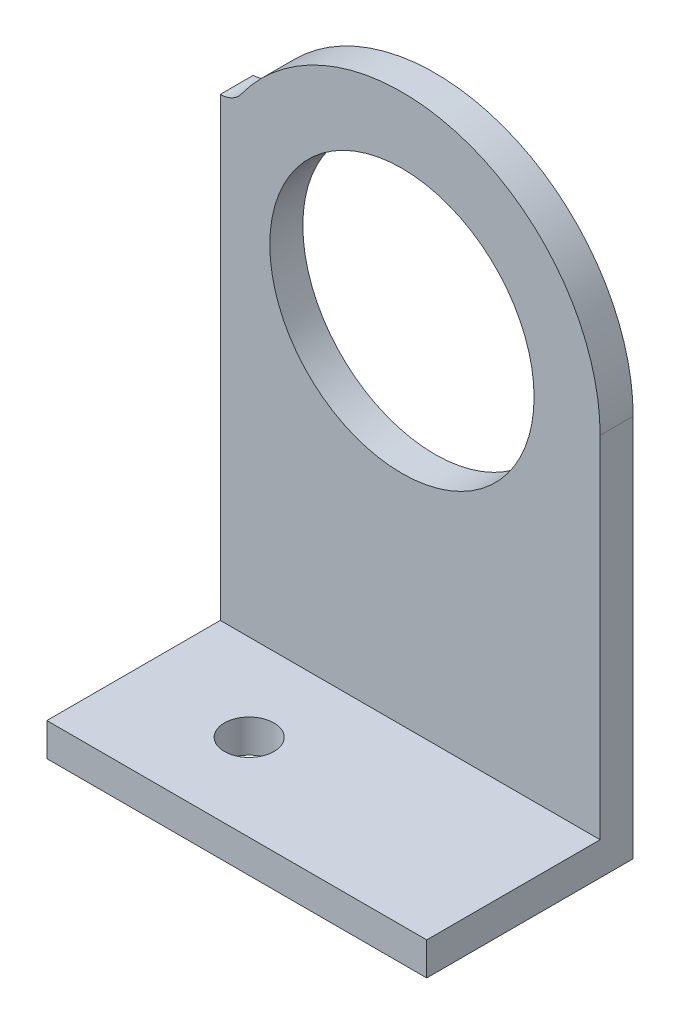
SolidWorks part; units mm, degrees
ref_plane "Front Plane" through (0, 0, 0) normal (0, 0, 1) x (1, 0, 0)
ref_plane "Top Plane" through (0, 0, 0) normal (0, 1, 0) x (1, 0, 0)
ref_plane "Right Plane" through (0, 0, 0) normal (1, 0, 0) x (0, 0, -1)
sketch "Sketch1" plane through (0, 0, 0) normal (0, 1, 0) x (1, 0, 0)
  line L1 (0, 0) -> (23, 0)
  line L2 (0, 0) -> (0, 12.5)
  line L3 (0, 12.5) -> (23, 12.5)
  line L4 (23, 0) -> (23, 12.5)
  dimension "D1" = 12.5
  dimension "D2" = 23
extrude "Boss-Extrude1" add sketch "Sketch1" along normal blind 2
sketch "Sketch2" plane through (0, 0, -12.5) normal (0, 0, -1) x (-1, 0, 0)
  line L1 (-23, 2) -> (0, 2)
  line L2 (-23, 2) -> (-23, 35.2062)
  line L3 (-23, 35.2062) -> (0, 35.2062)
  line L4 (0, 2) -> (0, 35.2062)
extrude "Boss-Extrude2" add sketch "Sketch2" against normal blind 2
sketch "Sketch3" plane through (0, 2, 0) normal (0, 1, 0) x (1, 0, 0)
  line L0 (0, 5.25) -> (23, 5.25) construction
  line L1 (0, 10.5) -> (0, 0) construction
  line L2 (23, 0) -> (23, 10.5) construction
  circle A0 centre (7, 5.25) radius 1.5
  dimension "D1" = 3
  dimension "D2" = 5.5
extrude "Cut-Extrude1" cut sketch "Sketch3" against normal blind 2 contours A0
sketch "Sketch4" plane through (0, 0, -12.5) normal (0, 0, -1) x (-1, 0, 0)
  line L1 (0, 35.2062) -> (0, 0) construction
  line L2 (0, 35.2062) -> (-23, 35.2062) construction
  circle A0 centre (-11, 23.2062) radius 8
  point P2 (-9.8668, 15.3728)
  point P3 (0, 0)
  point P4 (-10.1809, 18.5943)
  point P7 (-11, 20.2323)
  point P8 (0, 0)
  point P9 (-11, 19.1051)
  point P10 (-11, 20.214)
  dimension "D1" = 16
  dimension "D2" = 3
  dimension "D3" = 4
sketch "Sketch5" plane through (0, 0, -12.5) normal (0, 0, -1) x (-1, 0, 0)
sketch "Sketch6" plane through (0, 0, -12.5) normal (0, 0, -1) x (-1, 0, 0)
  line L0 (-23, 35.2062) -> (-23, 0) construction
  line L1 (0, 35.2062) -> (0, 0) construction
  arc A0 (-23, 23.2062) -> (-1.2728, 30.2334) centre (-11, 23.2062) cw
  arc A1 (-1.2728, 30.2334) -> (0, 29.5827) centre (0, 31.1529) ccw
extrude "Cut-Extrude2" cut sketch "Sketch4" against normal blind 2 contours A0
extrude "Cut-Extrude3" cut sketch "Sketch6" against normal blind 2 and the other way through all contours A0 A1
